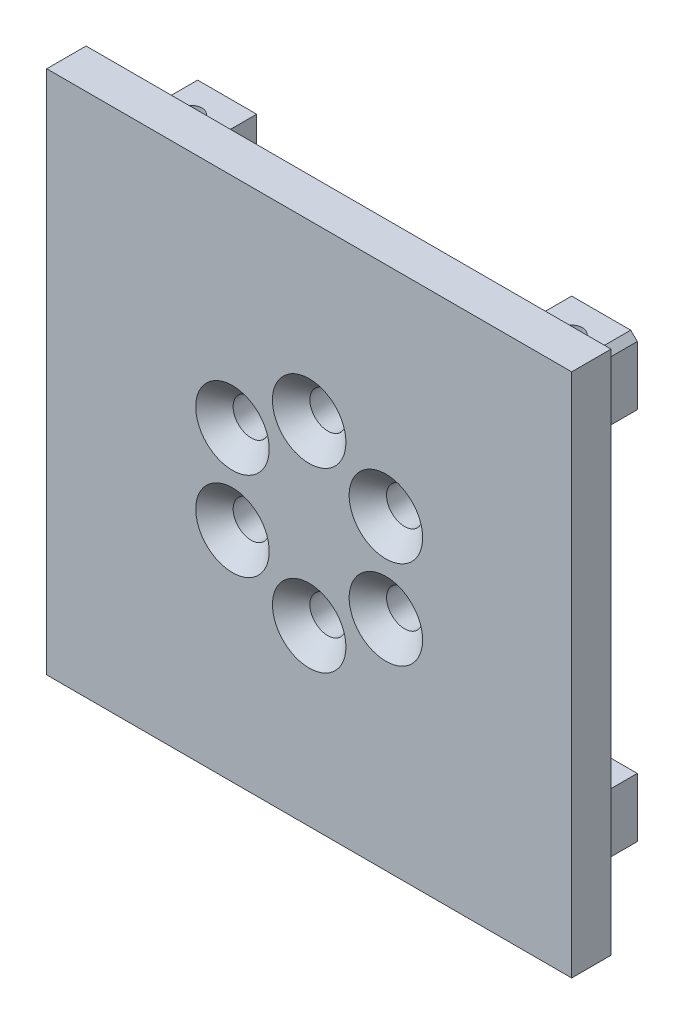
SolidWorks part; units mm, degrees
material "5052-O"
ref_plane "정면" through (0, 0, 0) normal (0, 0, 1) x (1, 0, 0)
ref_plane "윗면" through (0, 0, 0) normal (0, 1, 0) x (1, 0, 0)
ref_plane "우측면" through (0, 0, 0) normal (1, 0, 0) x (0, 0, -1)
sketch "스케치1" plane through (0, 0, 0) normal (0, 0, 1) x (1, 0, 0)
  line L1 (-40, 40) -> (40, 40)
  line L2 (-40, 40) -> (-40, -40)
  line L3 (-40, -40) -> (40, -40)
  line L4 (40, 40) -> (40, -40)
  line L5 (-40, 40) -> (40, -40) construction
  line L6 (-40, -40) -> (40, 40) construction
  point P0 (0, 0)
  dimension "D1" = 80
  dimension "D2" = 80
extrude "보스-돌출1" add sketch "스케치1" along normal blind 6
ref_axis "기준축1" through (0, 0, 0) along (0, 0, 1)
sketch "스케치11" plane through (0, 0, 0) normal (0, 0, -1) x (-1, 0, 0)
  line L0 (40, 40) -> (40, -40) construction
  line L1 (34, 34) -> (24, 34)
  line L2 (34, 34) -> (34, 24)
  line L3 (34, 24) -> (24, 24)
  line L4 (24, 34) -> (24, 24)
  line L5 (34, 34) -> (24, 24) construction
  line L6 (34, 24) -> (24, 34) construction
  line L7 (-40, 40) -> (40, 40) construction
  point P0 (29, 29)
  dimension "D1" = 10
  dimension "D2" = 10
  dimension "D3" = 6
  dimension "D4" = 6
extrude "보스-돌출3" add sketch "스케치11" along normal blind 10
hole_wizard "M4 나사 구멍2" positions "스케치12" profile "스케치13" tap size "M4" standard "ISO" end condition up to next
sketch "스케치12" plane through (0, 34, 0) normal (0, 1, 0) x (1, 0, 0)
  line L0 (-34, 10) -> (-34, 0) construction
  line L1 (-34, 10) -> (-24, 10) construction
  point P0 (-29, 5)
  point P6 (-34, 5)
  point P9 (-29, 10)
sketch "스케치13" plane through (-29, 34, -5) normal (1, 0, 0) x (0, 0, 1)
  line L0 (0, 0) -> (0, 68)
  line L1 (0, 68) -> (1.65, 68)
  line L2 (1.65, 68) -> (1.65, 0)
  line L5 (1.65, 0) -> (0, 0)
  line L11 (0, -6.35) -> (0, 107.95) construction
  dimension "관통 탭 드릴 지름" = 3.3
  dimension "관통 탭 드릴 깊이" = 68
cosmetic thread "구멍 나사산5" parameters "D2"=4
hole_wizard "M5 육각 소켓 접시 머리 캡 나사용 카운터싱크1" positions "스케치14" profile "스케치15" countersink size "M5" standard "ISO" end condition up to next
sketch "스케치14" plane through (0, 0, 6) normal (0, 0, 1) x (1, 0, 0)
  line L14 (0, -13.5) -> (11.6913, -6.75)
  line L15 (11.6913, -6.75) -> (11.6913, 6.75)
  line L16 (11.6913, 6.75) -> (0, 13.5)
  line L17 (0, 13.5) -> (-11.6913, 6.75)
  line L18 (-11.6913, 6.75) -> (-11.6913, -6.75)
  line L19 (-11.6913, -6.75) -> (0, -13.5)
  line L21 (-40, 40) -> (-40, -40) construction
  circle A1 centre (0, 0) radius 13.5 construction
  point P25 (0, -13.5)
  point P26 (11.6913, -6.75)
  point P27 (11.6913, 6.75)
  point P28 (0, 13.5)
  point P29 (-11.6913, 6.75)
  point P30 (-11.6913, -6.75)
  dimension "D1" = 27
sketch "스케치15" plane through (-11.6913, -6.75, 6) normal (1, 0, 0) x (0, -1, 0)
  line L0 (0, 0) -> (0, 6)
  line L1 (0, 6) -> (2.75, 6)
  line L2 (2.75, 6) -> (2.75, 2.85)
  line L3 (2.75, 2.85) -> (5.6, 0)
  line L5 (5.6, 0) -> (0, 0)
  line L6 (-2.75, 2.85) -> (-5.6, 0) construction
  line L11 (0, -6.35) -> (0, 107.95) construction
  dimension "관통 구멍 지름" = 5.5
  dimension "관통 구멍 깊이" = 6
  dimension "표면 카운터싱크 지름" = 11.2
  dimension "표면 카운터싱크 각도" = 90
mirror "대칭 복사1" about plane through (0, 0, 0) normal (1, 0, 0) of "M4 나사 구멍2", "보스-돌출3"
cosmetic thread "구멍 나사산6" parameters "D2"=4
mirror "대칭 복사2" about plane through (0, 0, 0) normal (0, 1, 0) of "대칭 복사1"
cosmetic thread "구멍 나사산7" parameters "D2"=4
cosmetic thread "구멍 나사산8" parameters "D2"=4
chamfer "모따기1" distance 1 angle 45 4 edges at (34, -34, -5) (34, 34, -5) (-34, 34, -5) (-34, -34, -5)
equation "\"D2@스케치1\"=\"D1@스케치1\""
equation "\"D2@스케치11\"=\"D1@스케치11\""
equation "\"D4@스케치11\"=\"D3@스케치11\""
